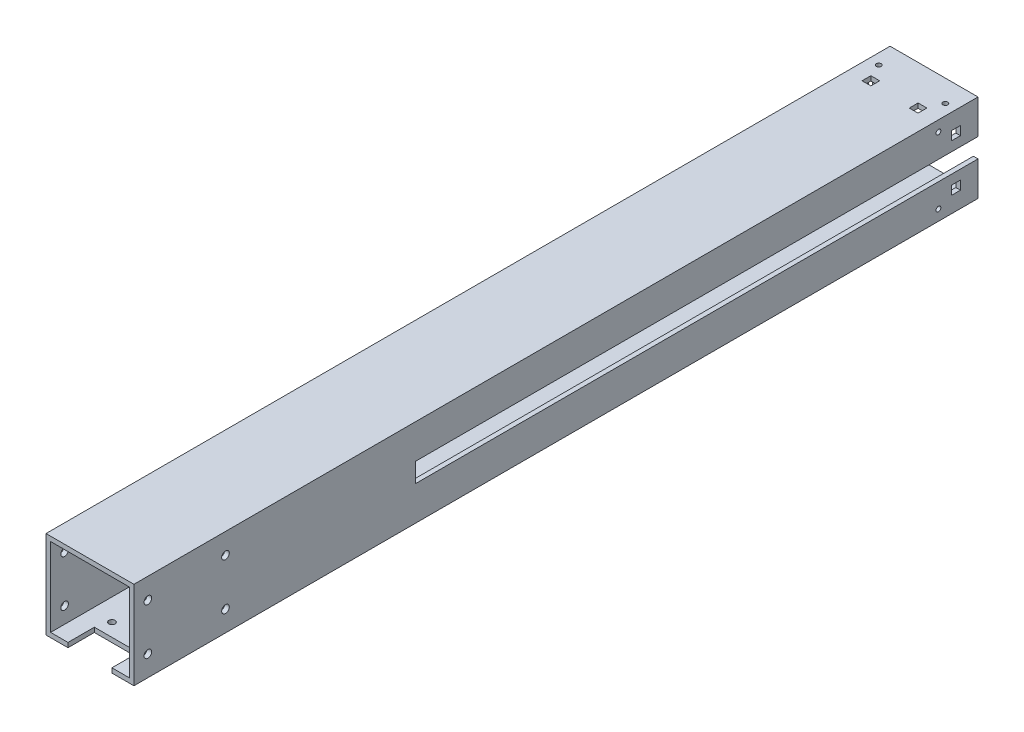
SolidWorks part; units mm, degrees
ref_plane "Front Plane" through (0, 0, 0) normal (1, 0, 0) x (0, 1, 0)
ref_plane "Top Plane" through (0, 0, 0) normal (0, 0, 1) x (0, 1, 0)
ref_plane "Right Plane" through (0, 0, 0) normal (0, 1, 0) x (-1, 0, 0)
sketch "Sketch1" plane through (0, 0, 0) normal (0, 0, 1) x (0, 1, 0)
  line L0 (28.4162, -28.4162) -> (28.4162, 28.4162)
  line L1 (31.75, -31.75) -> (-31.75, -31.75)
  line L2 (31.75, -31.75) -> (31.75, 31.75)
  line L3 (31.75, 31.75) -> (-31.75, 31.75)
  line L4 (-31.75, -31.75) -> (-31.75, 31.75)
  line L5 (31.75, -31.75) -> (-31.75, 31.75) construction
  line L6 (31.75, 31.75) -> (-31.75, -31.75) construction
  line L7 (28.4162, 28.4162) -> (-28.4162, 28.4162)
  line L8 (-28.4162, -28.4162) -> (-28.4162, 28.4162)
  line L9 (28.4162, -28.4162) -> (-28.4162, -28.4162)
  line L11 (6.985, -31.75) -> (-6.985, -31.75)
  line L12 (6.985, -31.75) -> (6.985, -28.4163)
  line L13 (6.985, -28.4163) -> (-6.985, -28.4163)
  line L14 (-6.985, -31.75) -> (-6.985, -28.4163)
  line L15 (6.985, -31.75) -> (-6.985, -28.4163) construction
  line L16 (6.985, -28.4163) -> (-6.985, -31.75) construction
  point P0 (0, 0)
  point P10 (0, -30.0831)
  dimension "D1" = 63.5
  dimension "D3" = 13.97
  dimension "D2" = 56.8325
extrude "Boss-Extrude1" add sketch "Sketch1" along normal blind 609.6 contours L1 L14 L9 L8 L7 L0 L12 L2 L3 L4 region at (0, 29.3143, 0)
sketch "Sketch2" plane through (0, 0, 0) normal (0, 1, 0) x (-1, 0, 0)
  line L0 (-28.4162, 0) -> (28.4162, 0) construction
  line L1 (-28.4162, 0) -> (28.4162, 0) construction
  line L2 (0, 0) -> (0, 609.6) construction
  line L3 (-31.75, 609.6) -> (31.75, 609.6) construction
  line L5 (22.225, 6.35) -> (-22.225, 6.35) construction
  line L6 (22.225, 6.35) -> (22.225, 19.05) construction
  line L7 (22.225, 19.05) -> (-22.225, 19.05) construction
  line L8 (-22.225, 6.35) -> (-22.225, 19.05) construction
  line L9 (22.225, 6.35) -> (-22.225, 19.05) construction
  line L10 (22.225, 19.05) -> (-22.225, 6.35) construction
  circle A3 centre (-22.225, 19.05) radius 1.75 construction
  circle A4 centre (22.225, 19.05) radius 1.75 construction
  circle A5 centre (22.225, 6.35) radius 1.75 construction
  circle A6 centre (-22.225, 6.35) radius 1.75 construction
  circle A7 centre (-24.05, 15.875) radius 1.75
  circle A8 centre (24.05, 15.875) radius 1.75
  point P2 (0, 12.7)
  dimension "D1" = 3.5
  dimension "D2" = 6.35
  dimension "D6" = 15.875
  dimension "D3" = 12.7
  dimension "D4" = 44.45
  dimension "D5" = 24.05
extrude "Cut-Extrude1" cut sketch "Sketch2" against normal blind 254 and the other way blind 254
sketch "Sketch4" plane through (31.75, 0, 0) normal (1, 0, 0) x (0, 1, 0)
  line L0 (-28.4162, 609.6) -> (-28.4162, 0) construction
  line L1 (-28.4162, 609.6) -> (-28.4162, 0) construction
  line L2 (-6.985, 0) -> (-31.75, 0) construction
  line L3 (0, 0) -> (0, 609.6) construction
  line L4 (-6.985, 609.6) -> (-31.75, 609.6) construction
  line L5 (31.75, 0) -> (6.985, 0) construction
  circle A1 centre (-22.225, 25.4) radius 1.75 construction
  circle A3 centre (-12.7, 12.7) radius 1.75 construction
  circle A6 centre (12.7, 12.7) radius 1.75 construction
  circle A7 centre (22.225, 25.4) radius 1.75 construction
  circle A8 centre (24.05, 28.575) radius 1.75
  circle A9 centre (-24.05, 28.575) radius 1.75
  dimension "D1" = 22.225
  dimension "D2" = 3.5
  dimension "D4" = 12.7
  dimension "D6" = 24.05
  dimension "D7" = 3.5
  dimension "D3" = 25.4
  dimension "D5" = 12.7
  dimension "D8" = 28.575
extrude "Cut-Extrude2" cut sketch "Sketch4" against normal blind 254
sketch "Sketch6" plane through (31.75, 0, 0) normal (1, 0, 0) x (0, 1, 0)
  line L0 (31.75, 14.125) -> (31.75, 17.625) construction
  line L5 (31.75, 14.125) -> (31.75, 17.625) construction
  line L6 (0, 0) -> (0, 19.05) construction
  line L7 (15.05, 20.875) -> (19.05, 20.875) construction
  line L8 (15.05, 20.875) -> (15.05, 10.875) construction
  line L9 (15.05, 10.875) -> (19.05, 10.875) construction
  line L10 (19.05, 20.875) -> (19.05, 10.875) construction
  line L11 (13.875, 19.05) -> (20.225, 19.05)
  line L12 (13.875, 19.05) -> (13.875, 12.7)
  line L13 (13.875, 12.7) -> (20.225, 12.7)
  line L14 (20.225, 19.05) -> (20.225, 12.7)
  line L15 (28.4163, 0) -> (-28.4162, 0) construction
  line L16 (-13.875, 12.7) -> (-20.225, 12.7)
  line L17 (-20.225, 19.05) -> (-20.225, 12.7)
  line L18 (-13.875, 19.05) -> (-20.225, 19.05)
  line L19 (-13.875, 19.05) -> (-13.875, 12.7)
  point P3 (0, 0)
  point P7 (31.75, 15.875)
  point P9 (19.05, 15.875)
  point P11 (17.05, 20.875)
  point P12 (20.225, 15.875)
  point P17 (17.05, 19.05)
  dimension "D1" = 10
  dimension "D2" = 4
  dimension "D3" = 19.05
  dimension "D4" = 6.35
  dimension "D5" = 6.35
extrude "Cut-Extrude4" cut sketch "Sketch6" against normal blind 90.678
sketch "Sketch7" plane through (0, 31.75, 0) normal (0, 1, 0) x (-1, 0, 0)
  line L0 (-31.75, 30.325) -> (-31.75, 26.825) construction
  line L1 (-31.75, 30.325) -> (-31.75, 26.825)
  line L2 (0, 0) -> (0, 31.75) construction
  line L3 (-19.05, 33.575) -> (-15.05, 33.575) construction
  line L4 (-19.05, 33.575) -> (-19.05, 23.575) construction
  line L5 (-19.05, 23.575) -> (-15.05, 23.575) construction
  line L6 (-15.05, 33.575) -> (-15.05, 23.575) construction
  line L7 (-20.225, 31.75) -> (-13.875, 31.75)
  line L8 (-20.225, 31.75) -> (-20.225, 25.4)
  line L9 (-20.225, 25.4) -> (-13.875, 25.4)
  line L10 (-13.875, 31.75) -> (-13.875, 25.4)
  line L11 (-31.75, 0) -> (31.75, 0) construction
  line L12 (20.225, 25.4) -> (13.875, 25.4)
  line L13 (13.875, 31.75) -> (13.875, 25.4)
  line L14 (20.225, 31.75) -> (13.875, 31.75)
  line L15 (20.225, 31.75) -> (20.225, 25.4)
  point P6 (-31.75, 28.575)
  point P7 (-19.05, 28.575)
  point P10 (-17.05, 33.575)
  point P14 (-20.225, 28.575)
  point P15 (-17.05, 31.75)
  dimension "D1" = 10
  dimension "D2" = 4
  dimension "D3" = 19.05
  dimension "D4" = 6.35
extrude "Cut-Extrude5" cut sketch "Sketch7" against normal blind 122.174 contours L10 L7 L8 L9 | L15 L14 L13 L12 region at (17.05, 31.75, 28.575) region at (-17.05, 31.75, 28.575)
sketch "Sketch8" plane through (31.75, 0, 0) normal (1, 0, 0) x (0, 1, 0)
  line L0 (31.75, 609.6) -> (31.75, 0) construction
  line L1 (-31.75, 609.6) -> (31.75, 609.6)
  line L2 (-31.75, 609.6) -> (-31.75, 406.4)
  line L3 (-31.75, 406.4) -> (31.75, 406.4)
  line L4 (31.75, 609.6) -> (31.75, 406.4)
  dimension "D1" = 203.2
extrude "Boss-Extrude2" add sketch "Sketch8" against normal up to surface (3.3338 mm away) up to face at (28.4162, -17.05, 15.875)
sketch "Sketch9" plane through (31.75, 0, 0) normal (1, 0, 0) x (0, 1, 0)
  line L0 (31.75, 609.6) -> (-31.75, 609.6) construction
  line L1 (16.812, 543.48) -> (-16.812, 543.48) construction
  line L2 (16.812, 543.48) -> (16.812, 599.52) construction
  line L3 (16.812, 599.52) -> (-16.812, 599.52) construction
  line L4 (-16.812, 543.48) -> (-16.812, 599.52) construction
  line L5 (16.812, 543.48) -> (-16.812, 599.52) construction
  line L6 (16.812, 599.52) -> (-16.812, 543.48) construction
  circle A0 centre (-16.812, 599.52) radius 2.75
  circle A1 centre (-16.812, 543.48) radius 2.75
  circle A2 centre (16.812, 543.48) radius 2.75
  circle A3 centre (16.812, 599.52) radius 2.75
  point P2 (0, 571.5)
  point P7 (0, 609.6)
  dimension "D1" = 5.5
  dimension "D2" = 33.624
  dimension "D3" = 56.04
  dimension "D4" = 38.1
extrude "Cut-Extrude6" cut sketch "Sketch9" against normal blind 100.584
sketch "Sketch11" plane through (0, -28.4162, 0) normal (0, 1, 0) x (-1, 0, 0)
  line L0 (-31.75, 609.6) -> (31.75, 609.6) construction
  line L1 (15.875, 609.6) -> (-15.875, 609.6)
  line L2 (15.875, 609.6) -> (15.875, 590.55)
  line L3 (15.875, 590.55) -> (-15.875, 590.55)
  line L4 (-15.875, 609.6) -> (-15.875, 590.55)
  circle A0 centre (-12.7, 581.025) radius 2.25
  circle A1 centre (12.7, 581.025) radius 2.25
  point P4 (0, 609.6)
  point P5 (0, 609.6)
  point P12 (0, 0)
  dimension "D3" = 4.5
  dimension "D6" = 25.4
  dimension "D1" = 31.75
  dimension "D2" = 19.05
  dimension "D4" = 9.525
  dimension "D5" = 12.7
extrude "Cut-Extrude8" cut sketch "Sketch11" against normal blind 31.496
